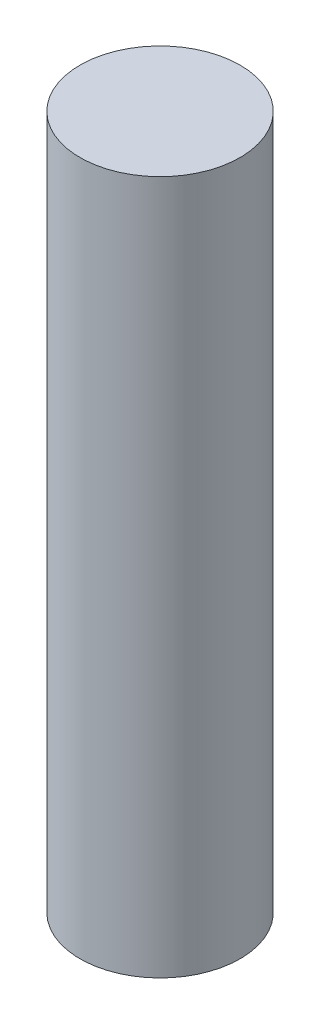
SolidWorks part; units mm, degrees
material "1023 Carbon Steel Sheet (SS)"
ref_plane "Front Plane" through (0, 0, 0) normal (0, 0, 1) x (1, 0, 0)
ref_plane "Top Plane" through (0, 0, 0) normal (0, 1, 0) x (1, 0, 0)
ref_plane "Right Plane" through (0, 0, 0) normal (1, 0, 0) x (0, 0, -1)
sketch "Sketch1" plane through (0, 0, 0) normal (0, 1, 0) x (1, 0, 0)
  circle A0 centre (0, 0) radius 3
  dimension "D1" = 6
extrude "Boss-Extrude1" add sketch "Sketch1" along normal blind 26 contours A0
